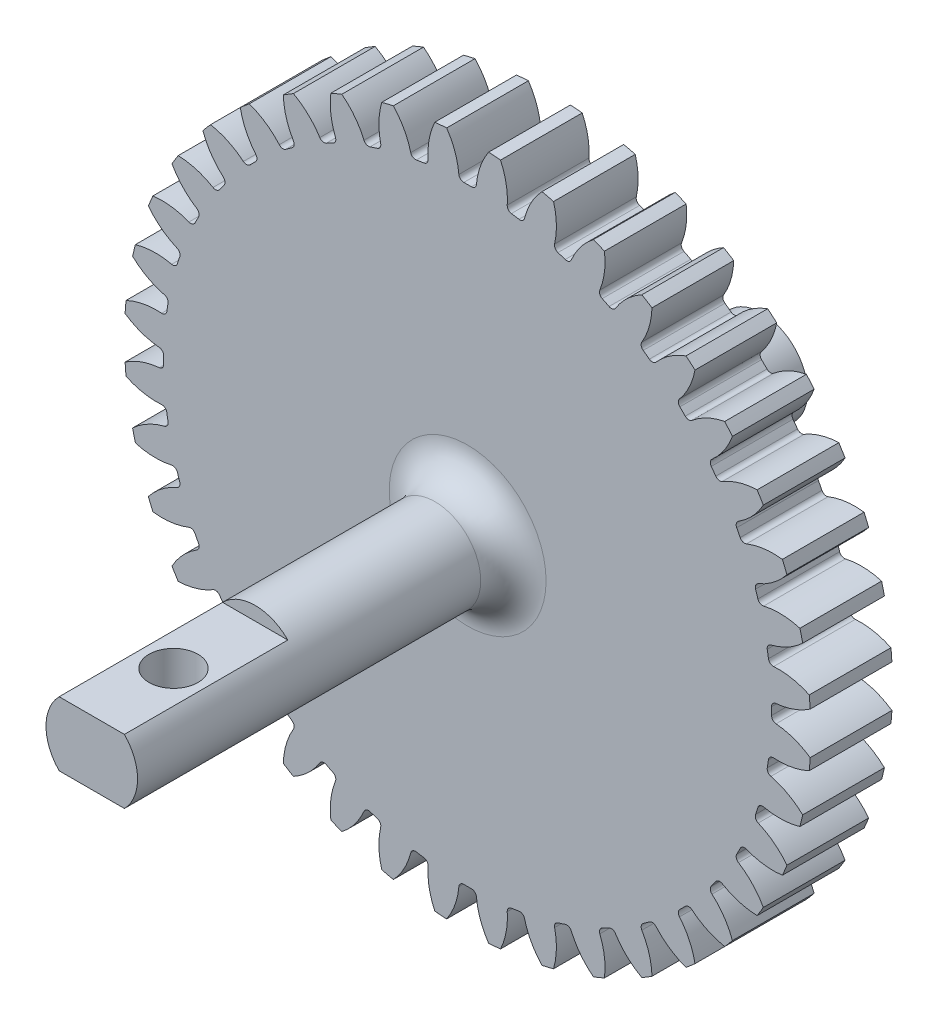
SolidWorks part; units mm, degrees
ref_plane "Front Plane" through (0, 0, 0) normal (0, 0, 1) x (1, 0, 0)
ref_plane "Top Plane" through (0, 0, 0) normal (0, 1, 0) x (1, 0, 0)
ref_plane "Right Plane" through (0, 0, 0) normal (1, 0, 0) x (0, 0, -1)
sketch "Sketch1" plane through (0, 0, 0) normal (0, 0, 1) x (1, 0, 0)
  circle A2 centre (0, 0) radius 20
  circle A3 centre (0, 0) radius 21
  circle A4 centre (0, 0) radius 18.6
  dimension "D1" = 40
  dimension "D2" = 42
  dimension "D3" = 2.4
extrude "Boss-Extrude1" add sketch "Sketch1" along normal mid plane 5 contours A3
sketch "Sketch3" plane through (0, 0, 2.5) normal (0, 0, 1) x (1, 0, 0)
  line L0 (0, 0) -> (0, 21) construction
  line L1 (-0.7852, 19.9846) -> (0.7852, 19.9846) construction
  line L2 (0, 0) -> (-0.5197, 18.5927) construction
  line L3 (0, 17.8273) -> (-1.5001, 21.9488) construction
  line L4 (0, 0) -> (1.6476, 20.9353) construction
  line L5 (0.7852, 19.9846) -> (2.3507, 19.8614) construction
  circle A0 centre (0, 0) radius 21 construction
  arc A1 (-2.1396, 21.8957) -> (-0.5197, 18.5927) centre (-4.9494, 18.4689) cw
  arc A2 (2.1396, 21.8957) -> (0.5197, 18.5927) centre (4.9494, 18.4689) ccw
  circle A3 centre (0, 0) radius 18.6 construction
  arc A4 (0.5197, 18.5927) -> (-0.5197, 18.5927) centre (0, 0) ccw
  circle A5 centre (0, 0) radius 20 construction
  circle A6 centre (0, 0) radius 21 construction
  circle A7 centre (0, 0) radius 22
  arc A8 (2.1396, 21.8957) -> (-2.1396, 21.8957) centre (0, 0) ccw
  dimension "D2" = 20
  dimension "D3" = 4.5
extrude "Cut-Extrude1" cut sketch "Sketch3" against normal through all both and the other way through all
fillet "Fillet1" radius 0.3 2 edges at (0.5197, 18.5927, 0) (-0.5197, 18.5927, 0)
pattern_circular "CirPattern1" count 40 over 360 about axis through (0, 0, 2.5) along (0, 0, -1) of "Cut-Extrude1", "Fillet1"
sketch "Sketch4" plane through (0, 0, 2.5) normal (0, 0, 1) x (1, 0, 0)
  line L0 (-1.3684, 2.5) -> (1.3684, 2.5)
  arc A0 (-1.3684, 2.5) -> (1.3684, 2.5) centre (0, 0) ccw
  dimension "D1" = 5.7
  dimension "D2" = 2.5
extrude "Cut-Extrude2" cut sketch "Sketch4" against normal through all both
sketch "Sketch5" plane through (0, 0, -2.5) normal (0, 0, -1) x (-1, 0, 0)
  circle A0 centre (0, 0) radius 2.8
  dimension "D1" = 5.6
extrude "Shaft" add sketch "Sketch5" against normal blind 28 and the other way blind 13
sketch "Sketch7" plane through (0, 0, 25.5) normal (0, 0, 1) x (1, 0, 0)
  circle A0 centre (0, 0) radius 2.9
  dimension "D1" = 5.8
extrude "Boss-Extrude2" add sketch "Sketch7" against normal blind 10
sketch "Sketch9" plane through (0, 0, 25.5) normal (0, 0, 1) x (1, 0, 0)
  line L0 (-2.2683, 1.9633) -> (2.2683, 1.9633)
  line L1 (0, 0) -> (1.9299, 0) construction
  line L2 (-2.2683, -1.9633) -> (2.2683, -1.9633)
  arc A0 (-2.2683, -1.9633) -> (2.2683, -1.9633) centre (0, 0) ccw
  arc A1 (2.2683, 1.9633) -> (-2.2683, 1.9633) centre (0, 0) ccw
  dimension "D1" = 1.9633
extrude "Cut-Extrude5" cut sketch "Sketch9" against normal blind 10
sketch "Sketch10" plane through (0, 1.9633, 0) normal (0, 1, 0) x (1, 0, 0)
  line L0 (-2.1343, -25.5) -> (2.1343, -25.5) construction
  circle A0 centre (0, -20.5) radius 1.5
  dimension "D1" = 3
  dimension "D2" = 5
extrude "Cut-Extrude6" cut sketch "Sketch10" against normal blind 8
sketch "Sketch11" plane through (0, 0, -2.5) normal (0, 0, -1) x (-1, 0, 0)
  circle A0 centre (0, 0) radius 4.2511
extrude "Boss-Extrude3" add sketch "Sketch11" against normal blind 5
fillet "Fillet4" radius 2 2 edges at (2.8, 0, -2.5) (2.8, 0, 2.5)
sketch "Sketch12" plane through (0, 0, 15.5) normal (0, 0, 1) x (1, 0, 0)
  circle A0 centre (0, 0) radius 2.8
  circle A1 centre (0, 0) radius 5.0238
  dimension "D1" = 5.6
extrude "Cut-Extrude7" cut sketch "Sketch12" along normal blind 10
equation "\"Module\"= 1mm"
equation "\"Number of Teeth\"= 40"
equation "\"D1@Sketch1\"=\"Module\" * \"Number of Teeth\""
equation "\"D2@Sketch1\"=(\"Number of Teeth\" + 2) * \"Module\""
equation "\"D3@Sketch1\"=\"Module\" * if( \"Module\"=>1.25,2.25,2.4)"
equation "\"D3@Sketch3\"=180 / \"Number of Teeth\""
equation "\"D1@Fillet1\"=0.3 * \"Module\""
equation "\"D1@CirPattern1\"=\"Number of Teeth\""
